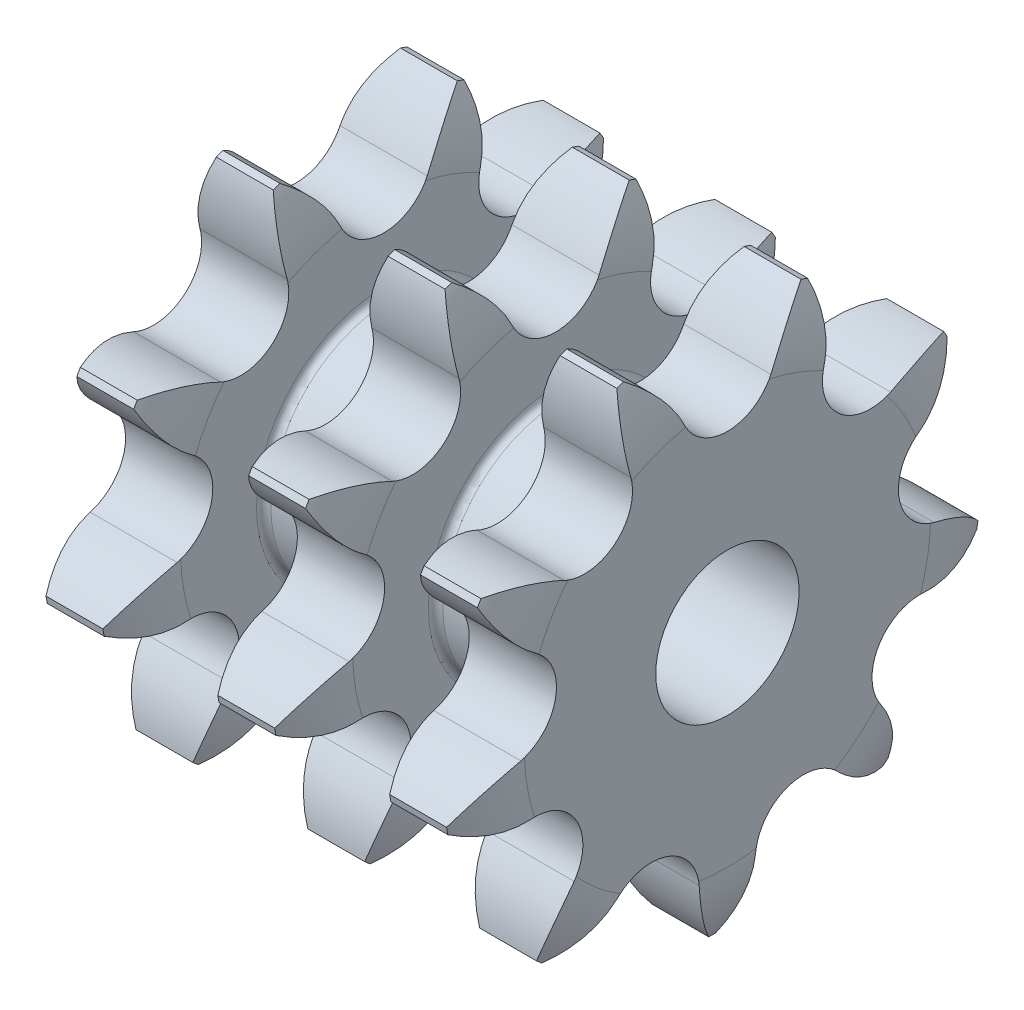
SolidWorks part; units mm, degrees
ref_plane "Plane1" through (0, 0, 0) normal (0, 0, 1) x (1, 0, 0)
ref_plane "Plane2" through (0, 0, 0) normal (0, 1, 0) x (1, 0, 0)
ref_plane "Plane3" through (0, 0, 0) normal (1, 0, 0) x (0, 0, -1)
sketch "Clipboard" plane through (0, 0, 0) normal (0, 1, 0) x (1, 0, 0)
  line L0 (0, 0) -> (12.5436, -1.9867)
  line L1 (-15, 0) -> (100, 0) construction
  line L2 (0, 0) -> (-0.8416, 0.9512)
  line L3 (0, 0) -> (-11.863, 4.5341)
  line L4 (0, 0) -> (3.0618, 0.4849)
  line L5 (0, 0) -> (-2.8109, -1.0484)
  line L6 (0, 0) -> (-29.8924, -20.1685)
  line L7 (-0.8416, 0.9512) -> (36.5829, 8.906)
  line L8 (-76.2, 38.1) -> (-75.2, 38.1)
  line L9 (-73.4321, 41.7084) -> (-72.837, 41.7846)
  line L10 (-73.4741, 12.9512) -> (-59.0941, 12.9512)
  circle A0 centre (0, 0) radius 3.975
  circle A1 centre (0, 0) radius 10.0465
  circle A2 centre (0, 0) radius 25
  dimension "Num_teeth" = 9
  dimension "Thickness" = 36.06
  dimension "Fillet_rad" = 0.6
sketch "BasProSke" plane through (0, 0, 0) normal (0, 1, 0) x (1, 0, 0)
  line L0 (-10, 0) -> (60, 0) construction
  line L1 (0, 0) -> (0, 16.9929)
  line L2 (0, 0) -> (36.06, 0)
  line L3 (36.06, 0) -> (36.06, 16.9929)
  line L4 (34.79, 22.5287) -> (1.27, 22.5287)
  arc A0 (0, 16.9929) -> (1.27, 22.5287) centre (12.7, 16.9929) cw
  arc A1 (36.06, 16.9929) -> (34.79, 22.5287) centre (23.36, 16.9929) ccw
  dimension "D1" = 12.7
  dimension "Thickness" = 36.06
  dimension "Diameter" = 45.0573
  dimension "G1" = 1.27
revolve "Base-Revolve" add sketch "BasProSke" angle 360 about L0
sketch "GrvSke" plane through (0, 0, 0) normal (0, 1, 0) x (1, 0, 0)
  line L0 (7.3, 16.9929) -> (7.3, 10.6465)
  line L1 (7.9, 10.0465) -> (13.78, 10.0465)
  line L2 (14.38, 10.6465) -> (14.38, 16.9929)
  line L3 (6.03, 22.5287) -> (15.65, 22.5287)
  line L4 (10.84, 0) -> (10.84, 52.07) construction
  line L5 (-10, 0) -> (60, 0) construction
  line L6 (0, 0) -> (35.56, 0) construction
  arc A0 (14.38, 16.9929) -> (15.65, 22.5287) centre (27.08, 16.9929) cw
  arc A1 (7.3, 16.9929) -> (6.03, 22.5287) centre (-5.4, 16.9929) ccw
  arc A2 (7.3, 10.6465) -> (7.9, 10.0465) centre (7.9, 10.6465) ccw
  arc A3 (13.78, 10.0465) -> (14.38, 10.6465) centre (13.78, 10.6465) ccw
  dimension "D1" = 12.7
  dimension "Diameter" = 45.0573
  dimension "Fillet_rad" = 0.6
  dimension "G1" = 1.27
  dimension "Grv_width" = 7.08
revolve "Groove" cut sketch "GrvSke" angle 360 about L6
pattern_linear "Grooves" count 2 spacing 14.38 along (1, 0, 0) of "Groove"
sketch "TooCutSke" plane through (0, 0, 0) normal (1, 0, 0) x (0, 0, -1)
  line L0 (0, 18.6059) -> (3.6386, 16.9092) construction
  line L1 (0, 0) -> (0, 107) construction
  line L2 (0, 18.6059) -> (-10, 18.6059) construction
  line L3 (0, 18.6059) -> (-3.6386, 16.9092) construction
  arc A0 (3.6386, 16.9092) -> (7.9748, 21.6037) centre (13.1494, 12.4742) cw
  arc A1 (3.6386, 16.9092) -> (-3.6386, 16.9092) centre (0, 18.6059) cw
  arc A2 (-3.6386, 16.9092) -> (-7.9748, 21.6037) centre (-13.1494, 12.4742) ccw
  arc A3 (7.9748, 21.6037) -> (-7.9748, 21.6037) centre (0, 0) ccw
extrude "ToothCut" cut sketch "TooCutSke" along normal through all
pattern_circular "TeethCuts" count 9 every 40 about axis through (-10, 0, 0) along (1, 0, 0) of "ToothCut"
sketch "HubNeaOneSke" plane through (0, 0, 0) normal (-1, 0, 0) x (0, 0, 1)
  circle A0 centre (0, 0) radius 10.0465
  dimension "Diameter" = 20.093
extrude "HubNearOne" [suppressed] add sketch "HubNeaOneSke" along normal blind 2.2005
fillet "HubNearOneFillet" [suppressed] radius 0.6
sketch "HubNeaBotSke" plane through (0, 0, 0) normal (-1, 0, 0) x (0, 0, 1)
  circle A0 centre (0, 0) radius 10.0465
  dimension "Diameter" = 20.093
extrude "HubNearBoth" [suppressed] add sketch "HubNeaBotSke" along normal blind 1.1003
fillet "HubNearBothFillet" [suppressed] radius 0.6
ref_plane "FarPln" through (36.06, 0, 0) normal (1, 0, 0) x (0, 0, -1)
sketch "HubFarSke" plane through (36.06, 0, 0) normal (1, 0, 0) x (0, 0, -1)
  circle A0 centre (0, 0) radius 10.0465
  dimension "Diameter" = 20.093
extrude "HubFar" [suppressed] add sketch "HubFarSke" along normal blind 1.1003
fillet "HubFarFillet" [suppressed] radius 0.6
sketch "BorSke" plane through (0, 0, 0) normal (1, 0, 0) x (0, 0, -1)
  circle A0 centre (0, 0) radius 6
  dimension "Diameter" = 12
extrude "Bore" cut sketch "BorSke" along normal mid plane 76.521
sketch "KeySke" plane through (0, 0, 0) normal (1, 0, 0) x (0, 0, -1)
  line L0 (-1, 0) -> (-1, 7)
  line L1 (-1, 7) -> (1, 7)
  line L2 (1, 7) -> (1, 0)
  line L3 (0, 0) -> (0, 34) construction
  line L4 (-1, 0) -> (1, 0)
  dimension "Offset" = 7
  dimension "Width" = 2
extrude "Keyway" [suppressed] cut sketch "KeySke" along normal mid plane 76.521
pattern_circular "Keyway2" [suppressed] count 2 every 90 about axis through (-10, 0, 0) along (1, 0, 0)
equation "' \"Pitch@Clipboard\" = 12.7"
equation "' \"Num_strands@Clipboard\" = 3"
equation "' \"Num_teeth@Clipboard\" = 9"
equation "' \"Hub_dia@Clipboard\" = 50"
equation "' \"Overall_len@Clipboard\" = 3"
equation "' \"Diameter@BorSke\" = 12"
equation "' \"T_dim@Clipboard\" = 1"
equation "' \"Width@KeySke\" = 2"
equation "' \"Dr@Clipboard\" = 7.95"
equation "' \"Face_width@Clipboard\" = 7.3"
equation "' \"Side_radius@Clipboard\" = 12.7"
equation "' \"Side_relief@Clipboard\" = 1.27"
equation "' \"Transv_pitch@Clipboard\" = 14.38"
equation "' \"Show_teeth@Clipboard\" = 9"
equation "' \"Fillet_rad@Clipboard\" = 0.6"
equation "' \"Plate_wid@Clipboard\" = 12"
equation "\"Num_teeth@Clipboard\" = int( \"Num_teeth@Clipboard\" )"
equation "\"Num_teeth@Clipboard\" = ((sgn( \"Num_teeth@Clipboard\" - 5.0)+1)*( \"Num_teeth@Clipboard\" - 5.0))/2 +5.0"
equation "\"Num_teeth@Clipboard\" = ((sgn( \"Num_teeth@Clipboard\" - 200.0)-1)*( \"Num_teeth@Clipboard\" - 200.0))/-2 +200.0"
equation "\"MHD@Clipboard\" = \"Pitch@Clipboard\" * (1.0 / tan(3.14159265 / \"Num_teeth@Clipboard\" )) - 1.05 * \"Plate_wid@Clipboard\" - 2.0 * \"Fillet_rad@Clipboard\" - 1.0"
equation "\"Thickness@Clipboard\"  = \"Face_width@Clipboard\" + (\"Num_strands@Clipboard\" - 1) * \"Transv_pitch@Clipboard\""
equation "\"OAL@Clipboard\" = \"Thickness@Clipboard\" + 2 * \"Fillet_rad@Clipboard\" + 1"
equation "\"MHD@Clipboard\" = ((sgn( \"MHD@Clipboard\" - \"Hub_dia@Clipboard\" )-1)*( \"MHD@Clipboard\" - \"Hub_dia@Clipboard\" ))/-2+ \"Hub_dia@Clipboard\""
equation "\"OAL@Clipboard\" = ((sgn( \"OAL@Clipboard\" - \"Overall_len@Clipboard\" )+1)*( \"OAL@Clipboard\" - \"Overall_len@Clipboard\" ))/2 + \"Overall_len@Clipboard\" + 0.0005"
equation "\"Num_teeth@TeethCuts\" = int( \"Show_teeth@Clipboard\" ) + 1"
equation "\"Num_teeth@TeethCuts\" = ((sgn( \"Num_teeth@TeethCuts\" - \"Num_teeth@Clipboard\" )-1)*( \"Num_teeth@TeethCuts\" - \"Num_teeth@Clipboard\" ))/-2+ \"Num_teeth@Clipboard\""
equation "\"Num_teeth@TeethCuts\" = ((sgn( \"Num_teeth@TeethCuts\" - 2.0)+1)*( \"Num_teeth@TeethCuts\" - 2.0))/2 +2.0"
equation "\"Angle@TeethCuts\" = 360.0 / \"Num_teeth@Clipboard\""
equation "\"Seat_radius@TooCutSke\" = ( \"Pitch@Clipboard\" / 2.0) / sin(3.14159265 / \"Num_teeth@Clipboard\" ) - \"Dr@Clipboard\" / 2.0 + \"Dr@Clipboard\" * 0.505"
equation "\"R1@TooCutSke\"  = \"Dr@Clipboard\" * 0.505"
equation "\"X@TooCutSke\" = 140.0 - (90.0 / \"Num_teeth@Clipboard\")"
equation "\"R2@TooCutSke\" = 0.12 * \"Dr@Clipboard\" * ( \"Num_teeth@Clipboard\" + 2.0)"
equation "\"Overcut@TooCutSke\" = 0.5 + 0.625 * \"Pitch@Clipboard\" - 0.5 * \"Dr@Clipboard\"  +  \"Pitch@Clipboard\" / 2.0 / sin(3.14159265 / \"Num_teeth@Clipboard\" )"
equation "\"Diameter@BasProSke\" = 2.0 * ( 0.625 * \"Pitch@Clipboard\" - 0.5 * \"Dr@Clipboard\"  +  \"Pitch@Clipboard\" / 2.0 / sin(3.14159265 / \"Num_teeth@Clipboard\" ))"
equation "\"Thickness@BasProSke\"  = \"Thickness@Clipboard\""
equation "\"G1@BasProSke\" =  \"Side_relief@Clipboard\""
equation "\"G2@BasProSke\" =  \"Side_relief@Clipboard\""
equation "\"D1@BasProSke\" =  \"Side_radius@Clipboard\""
equation "\"Diameter@GrvSke\" = \"Diameter@BasProSke\""
equation "\"G1@GrvSke\" = \"Side_relief@Clipboard\""
equation "\"D1@GrvSke\" = \"Side_radius@Clipboard\""
equation "\"Grv_diam@GrvSke\" =  \"Pitch@Clipboard\" * (1.0 / tan(3.14159265 / \"Num_teeth@Clipboard\" ))- 1.05 * \"Plate_wid@Clipboard\" - 2.0 * \"Fillet_rad@Clipboard\" - 1.0"
equation "\"Grv_width@GrvSke\" =  \"Transv_pitch@Clipboard\" - \"Face_width@Clipboard\""
equation "\"Offset@GrvSke\" = \"Grv_width@GrvSke\" / 2.0 + \"Face_width@Clipboard\""
equation "\"Fillet_rad@GrvSke\" = \"Fillet_rad@Clipboard\""
equation "\"Offset@Grooves\" = \"Transv_pitch@Clipboard\""
equation "\"Num_grvs@Grooves\" = \"Num_strands@Clipboard\""
equation "\"Num_grvs@Grooves\" = \"Num_grvs@Grooves\" - 1 * sgn( \"Num_grvs@Grooves\" -1)"
equation "\"Diameter@HubNeaOneSke\" = \"MHD@Clipboard\""
equation "\"Length@HubNearOne\" = \"OAL@Clipboard\" - \"Thickness@BasProSke\""
equation "\"Diameter@HubNeaBotSke\" = \"MHD@Clipboard\""
equation "\"Length@HubNearBoth\" = ( \"OAL@Clipboard\" - \"Thickness@BasProSke\" ) / 2.0"
equation "\"D1@HubNearOneFillet\" = \"Fillet_rad@Clipboard\""
equation "\"D1@HubNearBothFillet\" = \"Fillet_rad@Clipboard\""
equation "\"Thickness@FarPln\" = \"Thickness@BasProSke\""
equation "\"Diameter@HubFarSke\" = \"MHD@Clipboard\""
equation "\"Length@HubFar\" = ( \"OAL@Clipboard\" - \"Thickness@BasProSke\" ) / 2.0"
equation "\"D1@HubFarFillet\" = \"Fillet_rad@Clipboard\""
equation "\"D1@Bore\" = \"OAL@Clipboard\" * 2.0"
equation "\"D1@Keyway\" = \"OAL@Clipboard\" * 2.0"
equation "\"Offset@KeySke\" = \"T_dim@Clipboard\" + \"Diameter@BorSke\" / 2.0"
